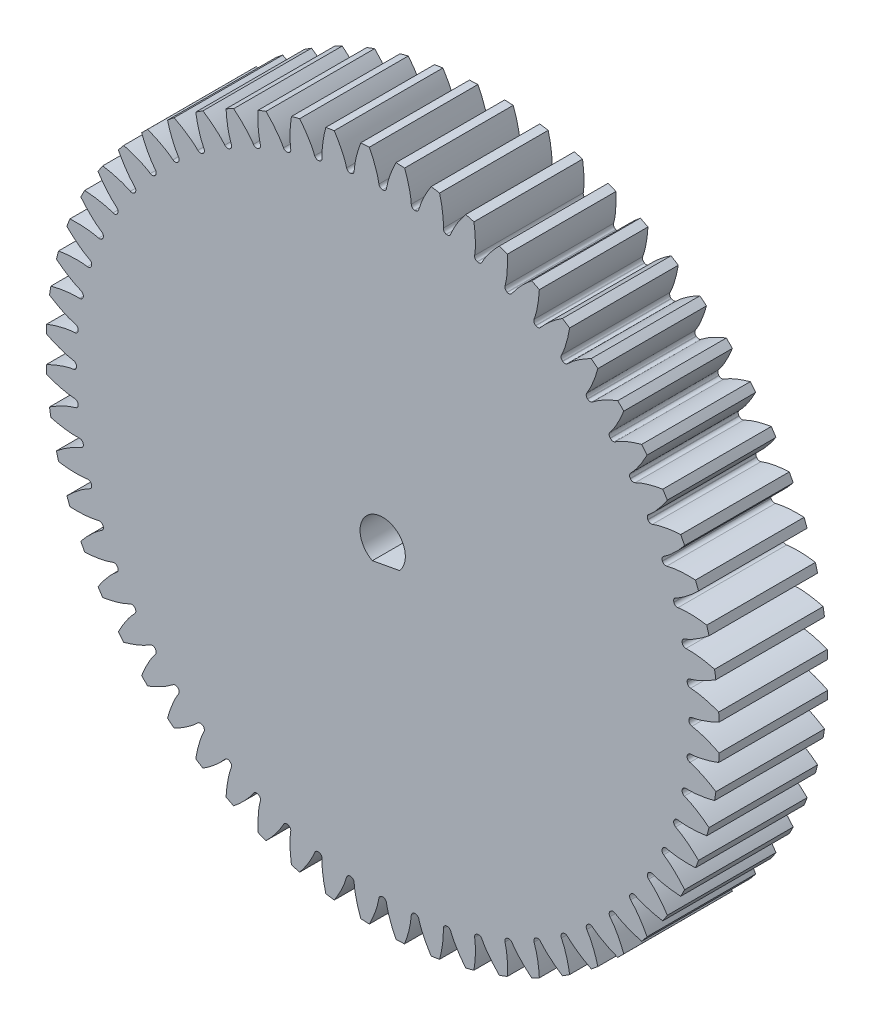
SolidWorks part; units mm, degrees
ref_plane "Front Plane" through (0, 0, 0) normal (0, 0, 1) x (1, 0, 0)
ref_plane "Top Plane" through (0, 0, 0) normal (0, 1, 0) x (1, 0, 0)
ref_plane "Right Plane" through (0, 0, 0) normal (1, 0, 0) x (0, 0, -1)
sketch "Sketch1" plane through (0, 0, 0) normal (0, 0, 1) x (1, 0, 0)
  line L0 (0, 0) -> (0, 38.1) construction
  line L1 (-12.2451, 42.5569) -> (12.2451, 33.6431) construction
  circle A0 centre (0, 0) radius 36.5125 construction
  circle A1 centre (0, 0) radius 39.37 construction
  circle A2 centre (0, 0) radius 38.1 construction
  circle A3 centre (0, 0) radius 35.8023 construction
  circle A4 centre (0, 0) radius 6.35 construction
  circle A5 centre (0, 0) radius 26.924 construction
  point P8 (254, 0)
  point P13 (762, 0)
  dimension "OD | Outside Diameter" = 78.74
  dimension "Root Diameter" = 73.025
  dimension "Gear Pitch Diameter" = 76.2
  dimension "Base Diameter" = 71.6046
  dimension "For Shaft Diameter" = 12.7
  dimension "Hub Diameter" = 53.848
  dimension "Pressure Angle" = 20
  dimension "Number of Teeth" = 1524
  dimension "Gear Pitch | Diametral Pitch" = 508
sketch "Sketch2" plane through (0, 0, 0) normal (1, 0, 0) x (0, 0, -1)
  line L0 (-6.35, 0) -> (6.35, 0) construction
  line L1 (-6.35, 39.37) -> (6.35, 39.37) construction
  point P2 (0, 39.37)
  point P4 (0, 0)
  point P6 (0, 39.37)
  dimension "Overall Width" = 12.7
  dimension "Hub Width" = 6.35
  dimension "Face Width" = 6.35
sketch "Sketch3" plane through (0, 0, 0) normal (0, 0, 1) x (1, 0, 0)
  circle A0 centre (0, 0) radius 39.37
  circle A1 centre (0, 0) radius 39.37 construction
extrude "Boss-Extrude1" add sketch "Sketch3" against normal up to vertex (6.35 mm away) and the other way up to vertex (6.35 mm away) up to point (0, 0, -6.35) other way up to point (0, 0, 6.35)
sketch "Sketch5" plane through (0, 0, 0) normal (1, 0, 0) x (0, 0, -1)
  line L1 (-6.35, 39.37) -> (0, 39.37)
  line L2 (-6.35, 39.37) -> (-6.35, 26.924)
  line L3 (-6.35, 26.924) -> (0, 26.924)
  line L4 (0, 39.37) -> (0, 26.924)
  line L11 (6.35, 6.35) -> (-6.35, 6.35)
  line L12 (6.35, 6.35) -> (6.35, 0)
  line L13 (6.35, 0) -> (-6.35, 0)
  line L14 (-6.35, 6.35) -> (-6.35, 0)
  point P5 (0, 6.35)
  point P12 (0, 26.924)
sketch "Sketch4" plane through (0, 0, 0) normal (0, 0, 1) x (1, 0, 0)
  line L0 (0, 0) -> (35.7999, 0.4037) construction
  line L2 (0, 0) -> (35.7999, -0.4037) construction
  line L4 (35.7999, 0.4037) -> (35.8, 0.4037)
  line L5 (35.8, -0.4037) -> (35.7999, -0.4037)
  arc A0 (35.7999, 0.4037) -> (35.7999, -0.4037) centre (0, 0) cw
  arc A3 (39.339, 1.5621) -> (39.339, -1.5621) centre (0, 0) cw
  circle A4 centre (0, 0) radius 39.37 construction
  spline S0 degree 4 poles (35.8, 0.4037) (35.8056, 0.4038) (35.8211, 0.4043) (35.8504, 0.4059) (35.8983, 0.4094) (35.9593, 0.4152) (36.0381, 0.4244) (36.1309, 0.4372) (36.2329, 0.4533) (36.3438, 0.4732) (36.4544, 0.4951) (36.5646, 0.5188) (36.6744, 0.5442) (36.8074, 0.5769) (36.9667, 0.6189) (37.1529, 0.6721) (37.3638, 0.7372) (37.5787, 0.8088) (37.7899, 0.8835) (38.0031, 0.9639) (38.2093, 1.0452) (38.4233, 1.1346) (38.6207, 1.2197) (38.8416, 1.3206) (39.0199, 1.4037) (39.2547, 1.5193) (39.3933, 1.5893) (39.5555, 1.6733) (39.6274, 1.7117) (39.6717, 1.7353) knots 0 0 0 0 0 0.005377 0.015084 0.028532 0.04661 0.064855 0.092111 0.119476 0.146842 0.174209 0.201575 0.228941 0.256307 0.307035 0.361767 0.4165 0.471232 0.525964 0.580697 0.635429 0.690161 0.744894 0.799626 0.854358 0.909091 0.954545 1 1 1 1 1 construction
  spline S1 degree 4 poles (35.8, 0.4037) (35.8056, 0.4038) (35.8211, 0.4043) (35.8504, 0.4059) (35.8983, 0.4094) (35.9593, 0.4152) (36.0381, 0.4244) (36.1309, 0.4372) (36.2329, 0.4533) (36.3438, 0.4732) (36.4544, 0.4951) (36.5646, 0.5188) (36.6744, 0.5442) (36.8074, 0.5769) (36.9667, 0.6189) (37.1529, 0.6721) (37.3638, 0.7372) (37.5787, 0.8088) (37.7899, 0.8835) (38.0031, 0.9639) (38.2093, 1.0452) (38.4233, 1.1346) (38.6207, 1.2197) (38.8416, 1.3206) (39.0199, 1.4037) (39.2038, 1.4942) (39.2933, 1.539) (39.339, 1.5621) knots 0 0 0 0 0 0.005377 0.015084 0.028532 0.04661 0.064855 0.092111 0.119476 0.146842 0.174209 0.201575 0.228941 0.256307 0.307035 0.361767 0.4165 0.471232 0.525964 0.580697 0.635429 0.690161 0.744894 0.799626 0.854358 0.909091 0.909091 0.909091 0.909091 0.909091
  spline S2 degree 4 poles (35.8, -0.4037) (35.8056, -0.4038) (35.8211, -0.4043) (35.8504, -0.4059) (35.8983, -0.4094) (35.9593, -0.4152) (36.0381, -0.4244) (36.1309, -0.4372) (36.2329, -0.4533) (36.3438, -0.4732) (36.4544, -0.4951) (36.5646, -0.5188) (36.6744, -0.5442) (36.8074, -0.5769) (36.9667, -0.6189) (37.1529, -0.6721) (37.3638, -0.7372) (37.5787, -0.8088) (37.7899, -0.8835) (38.0031, -0.9639) (38.2093, -1.0452) (38.4233, -1.1346) (38.6207, -1.2197) (38.8416, -1.3206) (39.0199, -1.4037) (39.2547, -1.5193) (39.3933, -1.5893) (39.5555, -1.6733) (39.6274, -1.7117) (39.6717, -1.7353) knots 0 0 0 0 0 0.005377 0.015084 0.028532 0.04661 0.064855 0.092111 0.119476 0.146842 0.174209 0.201575 0.228941 0.256307 0.307035 0.361767 0.4165 0.471232 0.525964 0.580697 0.635429 0.690161 0.744894 0.799626 0.854358 0.909091 0.954545 1 1 1 1 1 construction
  spline S3 degree 4 poles (35.8, -0.4037) (35.8056, -0.4038) (35.8211, -0.4043) (35.8504, -0.4059) (35.8983, -0.4094) (35.9593, -0.4152) (36.0381, -0.4244) (36.1309, -0.4372) (36.2329, -0.4533) (36.3438, -0.4732) (36.4544, -0.4951) (36.5646, -0.5188) (36.6744, -0.5442) (36.8074, -0.5769) (36.9667, -0.6189) (37.1529, -0.6721) (37.3638, -0.7372) (37.5787, -0.8088) (37.7899, -0.8835) (38.0031, -0.9639) (38.2093, -1.0452) (38.4233, -1.1346) (38.6207, -1.2197) (38.8416, -1.3206) (39.0199, -1.4037) (39.2038, -1.4942) (39.2933, -1.539) (39.339, -1.5621) knots 0 0 0 0 0 0.005377 0.015084 0.028532 0.04661 0.064855 0.092111 0.119476 0.146842 0.174209 0.201575 0.228941 0.256307 0.307035 0.361767 0.4165 0.471232 0.525964 0.580697 0.635429 0.690161 0.744894 0.799626 0.854358 0.909091 0.909091 0.909091 0.909091 0.909091
  dimension "D1" = 71.6043
extrude "Cut-Extrude1" cut sketch "Sketch4" against normal through all both and the other way through all
fillet "Fillet1" radius 0.4261 2 edges at (35.7999, -0.4037, 0) (35.7999, 0.4037, 0)
pattern_circular "CirPattern1" count 60 over 360 about axis through (0, 0, 6.35) along (0, 0, -1) of "Cut-Extrude1", "Fillet1"
sketch "Sketch6" plane through (0, 0, 6.35) normal (0, 0, 1) x (1, 0, 0)
  line L0 (-1.2068, -2.3593) -> (1.9718, -1.7705)
  circle A0 centre (0, 0) radius 2.65
  dimension "D1" = 5.3
  dimension "D2" = 2.1
extrude "Cut-Extrude2" cut sketch "Sketch6" against normal through all contours A0 region at (-0.0246, 0.1328, 6.35)
equation "\"Root Diameter@Sketch1\"=\"Root Diameter\""
equation "\"OD | Outside Diameter@Sketch1\"=\"Outside Diameter\""
equation "\"D1@CirPattern1\"=\"Number of Teeth\""
equation "\"Diametral Pitch\"=20"
equation "\"Number of Teeth\"= 60"
equation "\"Pressure Angle\"=20"
equation "\"Pitch Diameter\"= \"Number of Teeth\" / \"Diametral Pitch\""
equation "\"Base Diameter\"= \"Pitch Diameter\" * cos ( \"Pressure Angle\" )"
equation "\"Outside Diameter\"= ( \"Number of Teeth\" + 2 ) / \"Diametral Pitch\""
equation "\"Dedendum\"= 1.25 / \"Diametral Pitch\""
equation "\"Root Diameter\"= \"Pitch Diameter\" - ( 2 * \"Dedendum\" )"
equation "\"Pitch Angle\"= 360deg / \"Number of Teeth\""
equation "\"Alpha\"= sqr ( \"Pitch Diameter\" ^ 2 - \"Base Diameter\" ^ 2 ) / \"Base Diameter\" * 180 / PI - \"Pressure Angle\""
equation "\"Beta\"= ( \"Pitch Angle\" / 4 - \"Alpha\" )"
equation "\"Phi\"= sqr ( ( \"Outside Diameter\" / 2 ) ^ 2 - ( \"Base Diameter\" / 2 ) ^ 2 ) / ( \"Base Diameter\" / 2 )"
equation "\"Addendum\"= 1 / \"Diametral Pitch\""
equation "\"WorkingDepth\"= 2 / \"Diametral Pitch\""
equation "\"WholeDepth\"= 2.25 / \"Diametral Pitch\""
equation "\"Clearance\"= 0.25 / \"Diametral Pitch\""
equation "\"ToothThickness\"= ( pi * 2 ) / \"Diametral Pitch\""
equation "\"CircularPitch\"= pi / \"Diametral Pitch\""
equation "\"Number of Teeth@Sketch1\"=\"Number of Teeth\""
equation "\"Gear Pitch | Diametral Pitch@Sketch1\"=\"Diametral Pitch\""
equation "\"Pressure Angle@Sketch1\"=\"Pressure Angle\""
equation "\"Gear Pitch Diameter@Sketch1\"=\"Pitch Diameter\""
equation "\"Base Diameter@Sketch1\"=\"Base Diameter\""
equation "\"Fillet\"= \"Clearance\" * cos ( \"Pressure Angle\" ) * tan ( ( 90 + \"Pressure Angle\" ) / 2 )"
equation "\"D1@Fillet1\"=\"Fillet\""
equation "\"D1@Sketch4\"=if( \"Base Diameter\">\"Root Diameter\",\"Root Diameter\",\"Base Diameter\"-.00001)"
equation "\"D1@Fillet2\"=\"Fillet\""
